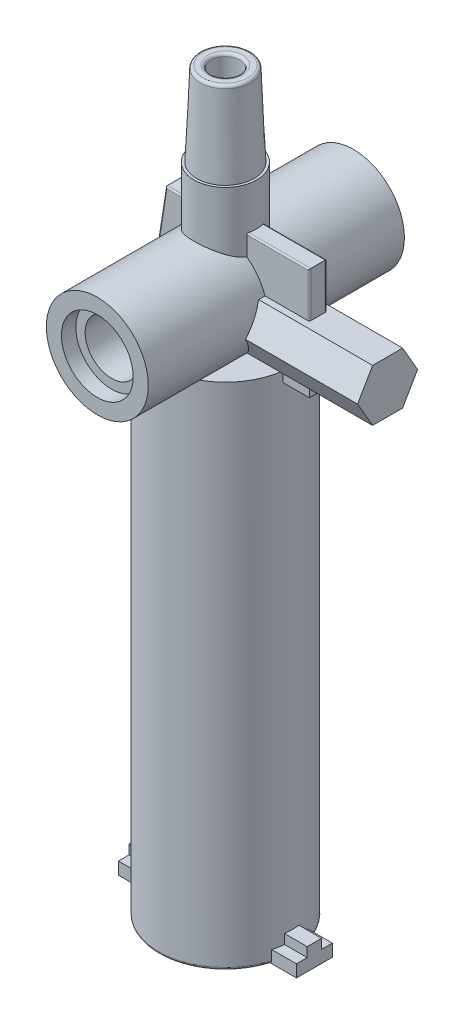
SolidWorks part; units mm, degrees
ref_plane "Front Plane" through (0, 0, 0) normal (0, 0, 1) x (1, 0, 0)
ref_plane "Top Plane" through (0, 0, 0) normal (0, 1, 0) x (1, 0, 0)
ref_plane "Right Plane" through (0, 0, 0) normal (1, 0, 0) x (0, 0, -1)
sketch "Sketch2" plane through (0, 0, 0) normal (0, 1, 0) x (1, 0, 0)
  circle A0 centre (0, 0) radius 4.65
  dimension "D1" = 9.3
extrude "Boss-Extrude2" add sketch "Sketch2" along normal blind 35.5
sketch "Sketch3" plane through (0, 0, 0) normal (0, 0, 1) x (1, 0, 0)
  line L0 (-4.65, 35.5) -> (-3.55, 42.55)
  line L1 (-3.55, 42.55) -> (6.45, 42.55)
  line L2 (6.45, 42.55) -> (6.45, 34.8)
  line L3 (6.45, 34.8) -> (-4.65, 34.8)
  line L4 (-4.65, 35.5) -> (-4.65, 0) construction
  line L5 (-4.65, 34.8) -> (-4.65, 35.5)
  dimension "D1" = 0.7
  dimension "D2" = 10
  dimension "D3" = 11.1
  dimension "D4" = 7.75
extrude "Boss-Extrude4" add sketch "Sketch3" along normal blind 0.6 and the other way blind 0.6
sketch "Sketch5" plane through (0, 0, 0.6) normal (0, 0, 1) x (1, 0, 0)
  line L0 (-4.65, 0) -> (4.65, 0) construction
  circle A0 centre (0, 38.25) radius 3.55
  dimension "D1" = 7.1
  dimension "D2" = 38.25
extrude "Boss-Extrude5" add sketch "Sketch5" along normal blind 8.32
sketch "Sketch6" plane through (0, 0, 8.92) normal (0, 0, 1) x (1, 0, 0)
  circle A0 centre (0, 38.25) radius 1.85
  dimension "D1" = 3.7
extrude "Cut-Extrude1" cut sketch "Sketch6" against normal blind 8.32
sketch "Sketch7" plane through (0, 0, 8.92) normal (0, 0, 1) x (1, 0, 0)
  circle A0 centre (0, 38.25) radius 2.5
  dimension "D1" = 5
extrude "Cut-Extrude2" cut sketch "Sketch7" against normal blind 1
mirror "Mirror1" about plane through (0, 0, 0) normal (0, 0, 1) of "Cut-Extrude1", "Boss-Extrude5", "Cut-Extrude2"
sketch "Sketch8" plane through (0, 35.5, 0) normal (0, 1, 0) x (1, 0, 0)
  circle A0 centre (0, 0) radius 2.175
  dimension "D1" = 4.35
extrude "Boss-Extrude6" add sketch "Sketch8" along normal blind 10
ref_plane "Plane1" through (0, 51.35, 0) normal (0, 1, 0) x (1, 0, 0)
sketch "Sketch10" plane through (0, 45.5, 0) normal (0, 1, 0) x (1, 0, 0)
  circle A0 centre (0, 0) radius 2
  point P3 (0, 0)
  dimension "D1" = 4
sketch "Sketch11" plane through (0, 51.35, 0) normal (0, 1, 0) x (1, 0, 0)
  circle A0 centre (0, 0) radius 1.75
  dimension "D1" = 3.5
loft "Loft1" add profiles "Sketch11", "Sketch10" connector at (1.3589, 51.35, -1.1027) connector at (1.7871, 45.5, -0.8979)
sketch "Sketch12" plane through (0, 0, 0) normal (1, 0, 0) x (0, 0, -1)
  line L0 (-4.65, 0) -> (4.65, 0) construction
  line L1 (1.045, 35.78) -> (2.09, 37.59)
  line L2 (2.09, 37.59) -> (1.045, 39.4)
  line L3 (1.045, 39.4) -> (-1.045, 39.4)
  line L4 (-1.045, 39.4) -> (-2.09, 37.59)
  line L5 (-2.09, 37.59) -> (-1.045, 35.78)
  line L6 (-1.045, 35.78) -> (1.045, 35.78)
  circle A0 centre (0, 37.59) radius 1.81 construction
  dimension "D1" = 4.18
  dimension "D2" = 39.4
extrude "Boss-Extrude7" add sketch "Sketch12" along normal blind 11.3
sketch "Sketch13" plane through (0, 51.35, 0) normal (0, 1, 0) x (1, 0, 0)
  circle A0 centre (0, 0) radius 1
  dimension "D1" = 2
extrude "Cut-Extrude3" cut sketch "Sketch13" against normal blind 20
sketch "Sketch15" plane through (0, 0, 0) normal (1, 0, 0) x (0, 0, -1)
  line L0 (-1.25, 0) -> (-1.25, 0.855)
  line L1 (-4.65, 0) -> (4.65, 0) construction
  line L2 (-1.25, 0.855) -> (-0.5, 0.855)
  line L3 (-0.5, 0.855) -> (-0.5, 1.5187)
  line L4 (-0.5, 1.5187) -> (0.5, 1.5187)
  line L5 (0.5, 1.5187) -> (0.5, 0.855)
  line L6 (0.5, 0.855) -> (1.25, 0.855)
  line L7 (1.25, 0.855) -> (1.25, 0)
  line L8 (1.25, 0) -> (-1.25, 0)
  line L9 (0, 0) -> (0, 2.8031) construction
  dimension "D1" = 1
  dimension "D2" = 2.5
extrude "Boss-Extrude8" add sketch "Sketch15" along normal blind 6.2 and the other way blind 6.2
fillet "Fillet1" radius 0.2 2 edges at (0, 51.35, 1) (0, 51.35, 1.75)
sketch "Sketch16" plane through (0, 0, 0) normal (0, -1, 0) x (1, 0, 0)
  circle A0 centre (0, 0) radius 3.45
  arc A1 (2.245, 4.0722) -> (-2.245, 4.0722) centre (0, 0) ccw construction
  dimension "D1" = 1.2
extrude "Cut-Extrude4" cut sketch "Sketch16" against normal blind 35.35
fillet "Fillet2" radius 0.2 2 edges at (0, 0, -4.65) (0, 0, 4.65)
fillet "Fillet3" radius 0.1 8 edges at (-2.8203, 42.55, 0.6) (-4.1, 39.025, 0.6) (-4.1, 39.025, -0.6) (-2.8203, 42.55, -0.6) (6.45, 40.975, 0.6) (6.45, 40.975, -0.6) (4.2703, 42.55, 0.6) (4.2703, 42.55, -0.6)
